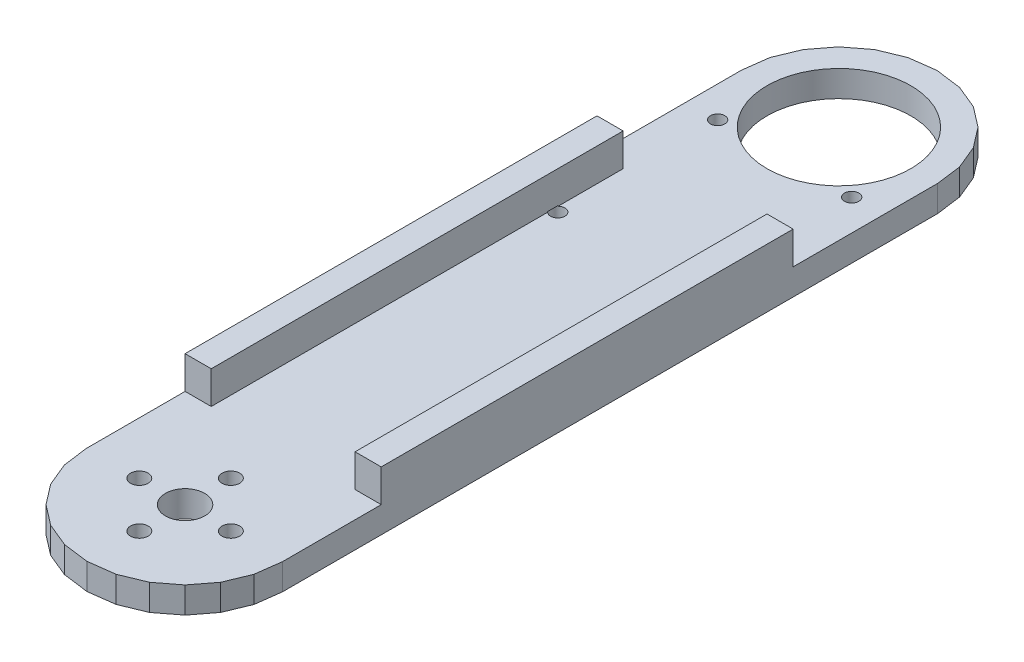
SolidWorks part; units mm, degrees
ref_plane "Front Plane" through (0, 0, 0) normal (0, 0, 1) x (1, 0, 0)
ref_plane "Top Plane" through (0, 0, 0) normal (0, 1, 0) x (1, 0, 0)
ref_plane "Right Plane" through (0, 0, 0) normal (1, 0, 0) x (0, 0, -1)
ref_plane "PY_p16_000" through (0, 16, 0) normal (0, 1, 0) x (1, 0, 0)
sketch "S_prism1" plane through (0, 16, 0) normal (0, 1, 0) x (1, 0, 0)
  line L0 (-15, -0.1) -> (-14.492, -3.956)
  line L1 (-14.492, -3.956) -> (-13.004, -7.55)
  line L2 (-13.004, -7.55) -> (-10.636, -10.636)
  line L3 (-10.636, -10.636) -> (-7.55, -13.004)
  line L4 (-7.55, -13.004) -> (-3.956, -14.492)
  line L5 (-3.956, -14.492) -> (-0.1, -15)
  line L6 (-0.1, -15) -> (0.1, -15)
  line L7 (0.1, -15) -> (3.956, -14.492)
  line L8 (3.956, -14.492) -> (7.55, -13.004)
  line L9 (7.55, -13.004) -> (10.636, -10.636)
  line L10 (10.636, -10.636) -> (13.004, -7.55)
  line L11 (13.004, -7.55) -> (14.492, -3.956)
  line L12 (14.492, -3.956) -> (15, -0.1)
  line L13 (15, -0.1) -> (15, 100.1)
  line L14 (15, 100.1) -> (14.492, 103.956)
  line L15 (14.492, 103.956) -> (13.004, 107.55)
  line L16 (13.004, 107.55) -> (10.636, 110.636)
  line L17 (10.636, 110.636) -> (7.55, 113.004)
  line L18 (7.55, 113.004) -> (3.956, 114.492)
  line L19 (3.956, 114.492) -> (0.1, 115)
  line L20 (0.1, 115) -> (-0.1, 115)
  line L21 (-0.1, 115) -> (-3.956, 114.492)
  line L22 (-3.956, 114.492) -> (-7.55, 113.004)
  line L23 (-7.55, 113.004) -> (-10.636, 110.636)
  line L24 (-10.636, 110.636) -> (-13.004, 107.55)
  line L25 (-13.004, 107.55) -> (-14.492, 103.956)
  line L26 (-14.492, 103.956) -> (-15, 100.1)
  line L27 (-15, 100.1) -> (-15, -0.1)
  dimension "P1" = 15
  dimension "P2" = 0.1
  dimension "P3" = 14.492
  dimension "P4" = 3.956
  dimension "P5" = 13.004
  dimension "P6" = 7.55
  dimension "P7" = 10.636
  dimension "P8" = 10.636
  dimension "P9" = 7.55
  dimension "P10" = 13.004
  dimension "P11" = 3.956
  dimension "P12" = 14.492
  dimension "P13" = 0.1
  dimension "P14" = 15
  dimension "P15" = 0.1
  dimension "P16" = 15
  dimension "P17" = 3.956
  dimension "P18" = 14.492
  dimension "P19" = 7.55
  dimension "P20" = 13.004
  dimension "P21" = 10.636
  dimension "P22" = 10.636
  dimension "P23" = 13.004
  dimension "P24" = 7.55
  dimension "P25" = 14.492
  dimension "P26" = 3.956
  dimension "P27" = 15
  dimension "P28" = 0.1
  dimension "P29" = 15
  dimension "P30" = 100.1
  dimension "P31" = 14.492
  dimension "P32" = 103.956
  dimension "P33" = 13.004
  dimension "P34" = 107.55
  dimension "P35" = 10.636
  dimension "P36" = 110.636
  dimension "P37" = 7.55
  dimension "P38" = 113.004
  dimension "P39" = 3.956
  dimension "P40" = 114.492
  dimension "P41" = 0.1
  dimension "P42" = 115
  dimension "P43" = 0.1
  dimension "P44" = 115
  dimension "P45" = 3.956
  dimension "P46" = 114.492
  dimension "P47" = 7.55
  dimension "P48" = 113.004
  dimension "P49" = 10.636
  dimension "P50" = 110.636
  dimension "P51" = 13.004
  dimension "P52" = 107.55
  dimension "P53" = 14.492
  dimension "P54" = 103.956
  dimension "P55" = 15
  dimension "P56" = 100.1
extrude "Boss_1" add sketch "S_prism1" along normal blind 4
ref_plane "PZ_m78_000" through (0, 0, -78) normal (0, 0, 1) x (1, 0, 0)
sketch "S_box2" plane through (0, 0, -78) normal (0, 0, 1) x (1, 0, 0)
  line L0 (-15, 19.5) -> (-11, 19.5)
  line L1 (-11, 19.5) -> (-11, 25)
  line L2 (-11, 25) -> (-15, 25)
  line L3 (-15, 25) -> (-15, 19.5)
  dimension "P1" = 15
  dimension "P2" = 19.5
  dimension "P3" = 11
  dimension "P4" = 19.5
  dimension "P5" = 11
  dimension "P6" = 25
  dimension "P7" = 15
  dimension "P8" = 25
extrude "Boss_2" add sketch "S_box2" along normal blind 63
sketch "S_box3" plane through (0, 0, -78) normal (0, 0, 1) x (1, 0, 0)
  line L0 (11, 19.5) -> (15, 19.5)
  line L1 (15, 19.5) -> (15, 25)
  line L2 (15, 25) -> (11, 25)
  line L3 (11, 25) -> (11, 19.5)
  dimension "P1" = 11
  dimension "P2" = 19.5
  dimension "P3" = 15
  dimension "P4" = 19.5
  dimension "P5" = 15
  dimension "P6" = 25
  dimension "P7" = 11
  dimension "P8" = 25
extrude "Boss_3" add sketch "S_box3" along normal blind 63
ref_plane "PY_p15_900" through (0, 15.9, 0) normal (0, 1, 0) x (1, 0, 0)
sketch "S_hole4" plane through (0, 15.9, 0) normal (0, 1, 0) x (1, 0, 0)
  circle A0 centre (0, 0) radius 3
  dimension "D1_S_hole4" = 6
extrude "Hole_4" cut sketch "S_hole4" along normal blind 4.2
sketch "S_hole5" plane through (0, 15.9, 0) normal (0, 1, 0) x (1, 0, 0)
  circle A0 centre (7, 0) radius 1.35
  dimension "D1_S_hole5" = 2.7
  dimension "P2" = 7
extrude "Hole_5" cut sketch "S_hole5" along normal blind 4.2
sketch "S_hole6" plane through (0, 15.9, 0) normal (0, 1, 0) x (1, 0, 0)
  circle A0 centre (0, -7) radius 1.35
  dimension "D1_S_hole6" = 2.7
  dimension "P2" = 7
extrude "Hole_6" cut sketch "S_hole6" along normal blind 4.2
sketch "S_hole7" plane through (0, 15.9, 0) normal (0, 1, 0) x (1, 0, 0)
  circle A0 centre (-7, 0) radius 1.35
  dimension "D1_S_hole7" = 2.7
  dimension "P2" = 7
extrude "Hole_7" cut sketch "S_hole7" along normal blind 4.2
sketch "S_hole8" plane through (0, 15.9, 0) normal (0, 1, 0) x (1, 0, 0)
  circle A0 centre (0, 7) radius 1.35
  dimension "D1_S_hole8" = 2.7
  dimension "P2" = 7
extrude "Hole_8" cut sketch "S_hole8" along normal blind 4.2
sketch "S_hole9" plane through (0, 15.9, 0) normal (0, 1, 0) x (1, 0, 0)
  circle A0 centre (0, 100) radius 11
  dimension "D1_S_hole9" = 22
  dimension "P2" = 100
extrude "Hole_9" cut sketch "S_hole9" along normal blind 4.2
sketch "S_hole10" plane through (0, 15.9, 0) normal (0, 1, 0) x (1, 0, 0)
  circle A0 centre (-10.25, 91.7) radius 1.1
  dimension "D1_S_hole10" = 2.2
  dimension "P2" = 10.25
  dimension "P3" = 91.7
extrude "Hole_10" cut sketch "S_hole10" along normal blind 4.2
sketch "S_hole11" plane through (0, 15.9, 0) normal (0, 1, 0) x (1, 0, 0)
  circle A0 centre (10.25, 91.7) radius 1.1
  dimension "D1_S_hole11" = 2.2
  dimension "P2" = 10.25
  dimension "P3" = 91.7
extrude "Hole_11" cut sketch "S_hole11" along normal blind 4.2
sketch "S_hole12" plane through (0, 15.9, 0) normal (0, 1, 0) x (1, 0, 0)
  circle A0 centre (-10.25, 67.25) radius 1.1
  dimension "D1_S_hole12" = 2.2
  dimension "P2" = 10.25
  dimension "P3" = 67.25
extrude "Hole_12" cut sketch "S_hole12" along normal blind 4.2
sketch "S_hole13" plane through (0, 15.9, 0) normal (0, 1, 0) x (1, 0, 0)
  circle A0 centre (10.25, 67.25) radius 1.1
  dimension "D1_S_hole13" = 2.2
  dimension "P2" = 10.25
  dimension "P3" = 67.25
extrude "Hole_13" cut sketch "S_hole13" along normal blind 4.2
equation "\"plate_t\" = 3"
equation "\"clearance\" = 0.4"
